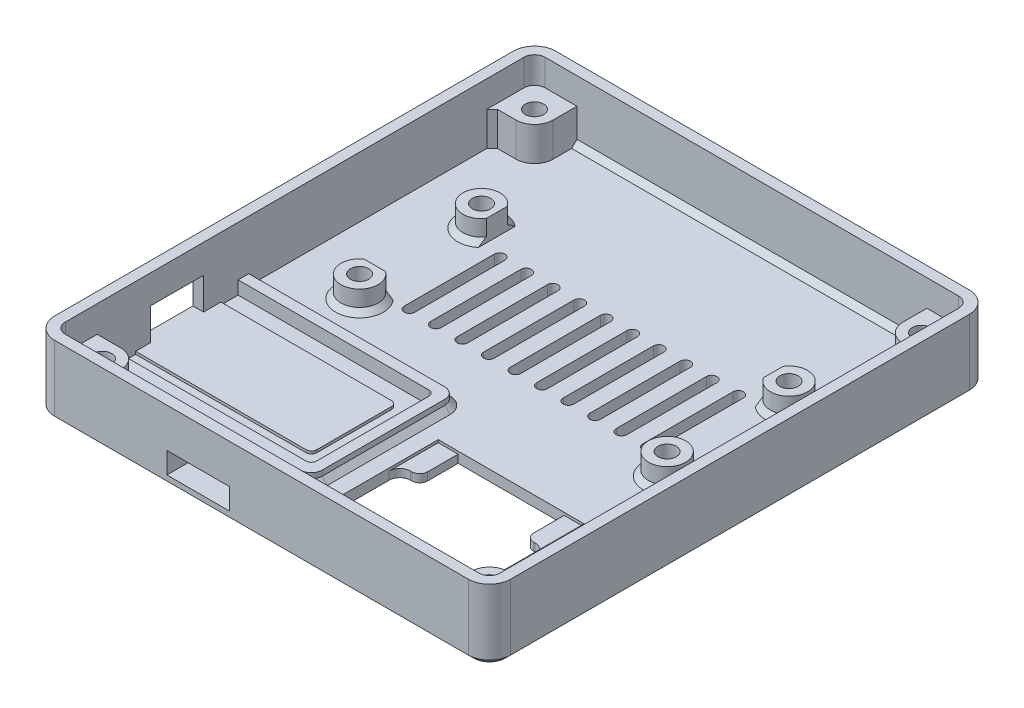
SolidWorks part; units mm, degrees
ref_plane "Front Plane" through (0, 0, 0) normal (0, 0, 1) x (1, 0, 0)
ref_plane "Top Plane" through (0, 0, 0) normal (0, 1, 0) x (1, 0, 0)
ref_plane "Right Plane" through (0, 0, 0) normal (1, 0, 0) x (0, 0, -1)
sketch "Sketch1" plane through (0, 0, 0) normal (0, 1, 0) x (1, 0, 0)
  line L0 (-65.617, -16.3721) -> (-0.617, -16.3721)
  line L1 (-62.117, 10.1279) -> (-4.117, 10.1279)
  line L2 (-62.117, 10.1279) -> (-62.117, -12.8721)
  line L3 (-65.617, 13.6279) -> (-0.617, 13.6279)
  line L4 (-65.617, 13.6279) -> (-65.617, -16.3721)
  line L5 (-62.117, -12.8721) -> (-4.117, -12.8721)
  line L6 (-0.617, 13.6279) -> (-0.617, -16.3721)
  line L7 (-4.117, 10.1279) -> (-4.117, -12.8721)
  line L8 (-24.217, 16.7282) -> (-24.217, 15.4455)
  line L9 (-11.617, 16.7282) -> (-11.617, 15.4455)
  dimension "D1" = 65
  dimension "D2" = 30
  dimension "D3" = 58
  dimension "D4" = 23
  dimension "D5" = 3.5
  dimension "D6" = 3.5
sketch "Sketch2" plane through (0, 0, 0) normal (0, 1, 0) x (1, 0, 0)
  line L0 (-0.617, 13.6279) -> (-0.617, -16.3721) construction
  line L6 (-74.617, 13.6279) -> (-74.617, -16.3721)
  line L7 (-74.617, 30.6279) -> (-74.617, -55.8721)
  line L10 (-72.617, -57.8721) -> (5.383, -57.8721)
  line L11 (-76.617, -1.6221) -> (-76.617, -55.8721)
  line L14 (7.383, 30.6279) -> (7.383, -55.8721)
  line L15 (-72.617, 32.6279) -> (5.383, 32.6279)
  line L16 (-72.617, -59.8721) -> (5.383, -59.8721)
  line L17 (9.383, 30.6279) -> (9.383, -1.6221)
  line L18 (-72.617, 34.6279) -> (5.383, 34.6279)
  line L24 (-76.617, 30.6279) -> (-76.617, -55.8721) construction
  line L25 (-76.617, 30.6279) -> (-76.617, -1.6221)
  line L26 (9.383, 30.6279) -> (9.383, -55.8721) construction
  line L27 (9.383, -1.6221) -> (9.383, -55.8721)
  line L28 (-65.617, 13.6279) -> (-0.617, 13.6279) construction
  line L29 (-65.617, -16.3721) -> (-0.617, -16.3721) construction
  arc A0 (-72.617, -57.8721) -> (-74.617, -55.8721) centre (-72.617, -55.8721) cw
  arc A1 (5.383, -57.8721) -> (7.383, -55.8721) centre (5.383, -55.8721) ccw
  arc A2 (7.383, 30.6279) -> (5.383, 32.6279) centre (5.383, 30.6279) ccw
  arc A3 (-72.617, 32.6279) -> (-74.617, 30.6279) centre (-72.617, 30.6279) ccw
  arc A4 (-72.617, -59.8721) -> (-76.617, -55.8721) centre (-72.617, -55.8721) cw
  arc A5 (5.383, -59.8721) -> (9.383, -55.8721) centre (5.383, -55.8721) ccw
  arc A6 (9.383, 30.6279) -> (5.383, 34.6279) centre (5.383, 30.6279) ccw
  arc A7 (-72.617, 34.6279) -> (-76.617, 30.6279) centre (-72.617, 30.6279) ccw
  point P62 (-76.617, -11.6221)
  point P67 (9.383, -31.6221)
  dimension "D4" = 19
  dimension "D2" = 8
  dimension "D14" = 41.5
  dimension "D1" = 9
  dimension "D5" = 2
extrude "Boss-Extrude1" add sketch "Sketch2" along normal blind 13.4 contours L17 A6 L18 A7 L25 L11 A4 L16 A5 L27 A3 L15 A2 L14 A1 L10 A0 L7 region at (-75.3392, 0, -14.5029)
extrude "Boss-Extrude2" add sketch "Sketch2<3>" along normal blind 2 contours L15 A3 L7 A0 L10 A1 L14 A2 region at (-33.617, 0, 12.6221)
sketch "Sketch2<3>" plane through (0, 0, 0) normal (0, 1, 0) x (1, 0, 0) same geometry as "Sketch2"
sketch "Sketch4" plane through (0, 2, 0) normal (0, 1, 0) x (1, 0, 0)
  line L0 (-59.2343, 12.1129) -> (-59.2343, 8.1428)
  line L9 (-64.1397, -10.0158) -> (-60.0943, -10.0158)
  line L12 (-7.0825, 11.9868) -> (-7.0825, 8.269)
  arc A0 (-7.0825, 8.269) -> (-7.0825, 11.9868) centre (-4.117, 10.1279) ccw
  arc A1 (-7.0825, 8.269) -> (-0.617, 10.1279) centre (-4.117, 10.1279) ccw
  arc A2 (-64.1397, -10.0158) -> (-60.0943, -10.0158) centre (-62.117, -12.8721) ccw
  arc A3 (-65.617, 10.1279) -> (-59.2343, 8.1428) centre (-62.117, 10.1279) ccw
  arc A4 (-59.2343, 12.1129) -> (-59.2343, 8.1428) centre (-62.117, 10.1279) ccw
  circle A5 centre (-4.117, -12.8721) radius 3.5
extrude "Boss-Extrude3" add sketch "Sketch4" along normal offset from surface (4 mm away) 7.4 contours L12 A0 | L0 A4 A3 | L9 A2 | A5 region at (-62.2586, 2, -10.1279) region at (-62.117, 2, 13.0224) region at (-4.0017, 2, -10.1279) region at (-4.117, 2, 12.8721) up to face at (-33.617, 13.4, 12.6221)
hole_wizard "CSK for #4 Flat Head Socket Cap Screw1" positions "Sketch6" profile "Sketch5" countersink size "#4" standard "ANSI Inch" end condition through all
sketch "Sketch6" plane through (0, 0, 0) normal (0, -1, 0) x (-1, 0, 0)
  point P0 (4.117, 10.1279)
  point P4 (62.117, 10.1279)
  point P8 (4.117, -12.8721)
  point P12 (62.117, -12.8721)
sketch "Sketch5" plane through (-4.117, 0, -10.1279) normal (1, 0, 0) x (0, 0, -1)
  line L0 (0, 0) -> (0, 13.4)
  line L1 (0, 13.4) -> (1.7272, 13.4)
  line L2 (1.7272, 13.4) -> (1.7272, 1.8805)
  line L3 (1.7272, 1.8805) -> (3.3619, 0)
  line L5 (3.3619, 0) -> (0, 0)
  line L6 (-1.7272, 1.8805) -> (-3.3619, 0) construction
  line L11 (0, -6.35) -> (0, 107.95) construction
  dimension "Thru Hole Dia." = 3.4544
  dimension "Thru Hole Depth" = 13.4
  dimension "Near C'Sink Dia." = 6.7237
  dimension "Near C'Sink Angle" = 82
sketch "Sketch15" plane through (0, 2, 0) normal (0, 1, 0) x (1, 0, 0)
  line L1 (-74.617, -23.279) -> (-37.617, -23.279)
  line L2 (-74.617, -21.279) -> (-74.617, -23.279)
  line L3 (-74.617, -46.479) -> (-37.617, -46.479)
  line L4 (-37.617, -23.279) -> (-37.617, -46.479)
  line L5 (-74.617, -21.279) -> (-35.617, -21.279)
  line L6 (-35.617, -21.279) -> (-35.617, -48.479)
  line L7 (-74.617, -48.479) -> (-35.617, -48.479)
  line L8 (-74.617, -46.479) -> (-74.617, -48.479)
  dimension "D1" = 23.2
extrude "Boss-Extrude5" add sketch "Sketch15" along normal blind 2
fillet "Fillet1" radius 1 1 edges at (-37.617, 3, 23.279)
fillet "Fillet2" radius 1 1 edges at (-37.617, 3, 46.479)
fillet "Fillet3" radius 2 2 edges at (-35.617, 3, 48.479) (-35.617, 3, 21.279)
sketch "Sketch16" plane through (-74.617, 0, 0) normal (1, 0, 0) x (0, 0, -1)
  line L1 (-39.8053, 2) -> (-29.8053, 2)
  line L2 (-39.8053, 2) -> (-39.8053, 8)
  line L3 (-39.8053, 8) -> (-29.8053, 8)
  line L4 (-29.8053, 2) -> (-29.8053, 8)
  dimension "D1" = 6
  dimension "D2" = 10
extrude "Cut-Extrude4" cut sketch "Sketch16" against normal up to next
sketch "Sketch9" plane through (0, 2, 0) normal (0, 1, 0) x (1, 0, 0)
  line L0 (7.383, 30.6279) -> (7.383, -55.8721) construction
  line L1 (2.883, -49.8721) -> (7.383, -49.8721)
  line L2 (-0.617, 32.6279) -> (5.383, 32.6279)
  line L3 (7.3733, 24.6279) -> (7.383, 30.6246)
  line L4 (-0.617, -53.3721) -> (-0.617, -57.8721)
  line L5 (-66.617, 32.6279) -> (-72.617, 32.6279)
  line L6 (-0.617, 28.1279) -> (-0.617, 32.6279)
  line L7 (-0.617, -57.8721) -> (5.383, -57.8721)
  line L8 (2.883, 24.6279) -> (7.3733, 24.6279)
  line L9 (7.383, -49.8721) -> (7.383, -55.8721)
  line L10 (-66.617, -53.3721) -> (-66.617, -57.8721)
  line L11 (-74.6073, -49.8721) -> (-74.617, -55.8689)
  line L12 (-70.117, 24.6279) -> (-74.617, 24.6279)
  line L13 (-66.617, 28.1279) -> (-66.617, 32.6279)
  line L14 (-70.117, -49.8721) -> (-74.6073, -49.8721)
  line L15 (-66.617, -57.8721) -> (-72.617, -57.8721)
  line L16 (-74.617, 24.6279) -> (-74.617, 30.6279)
  line L18 (-72.617, -57.8721) -> (5.383, -57.8721) construction
  arc A0 (2.883, -49.8721) -> (-0.617, -53.3721) centre (2.883, -53.3721) ccw
  arc A1 (5.383, 32.6279) -> (7.383, 30.6246) centre (5.383, 30.6279) cw
  arc A2 (7.383, -55.8721) -> (5.383, -57.8721) centre (5.383, -55.8721) cw
  arc A3 (-0.617, 28.1279) -> (2.883, 24.6279) centre (2.883, 28.1279) ccw
  arc A4 (-72.617, -57.8721) -> (-74.617, -55.8689) centre (-72.617, -55.8721) cw
  arc A5 (-70.117, 24.6279) -> (-66.617, 28.1279) centre (-70.117, 28.1279) ccw
  arc A6 (-74.617, 30.6279) -> (-72.617, 32.6279) centre (-72.617, 30.6279) cw
  arc A7 (-66.617, -53.3721) -> (-70.117, -49.8721) centre (-70.117, -53.3721) ccw
  dimension "D1" = 4.5
  dimension "D2" = 2
  dimension "D3" = 2
extrude "Boss-Extrude4" add sketch "Sketch9" along normal offset from surface (6.4 mm away) 5 up to face at (-33.617, 13.4, 12.6221)
chamfer "Chamfer1" distance 1 angle 45 4 edges at (-0.617, 5.2, 57.8721) (7.383, 5.2, 49.8721) (-74.617, 5.2, -24.6279) (-66.617, 5.2, 57.8721)
chamfer "Chamfer2" distance 1 angle 45 15 edges at (-62.117, 2, 16.3721) (-65.617, 2, -10.1279) (7.383, 2, 9.1238) (-33.617, 2, 57.8721) (-33.617, 2, -32.6279) (-0.617, 2, -10.1279) (-0.617, 2, 55.1221) (0.4081, 2, 50.8973) (-4.117, 2, 16.3721) (-56.117, 2, 48.479) (-56.117, 2, 21.279) (-36.2028, 2, 47.8932) (-36.2028, 2, 21.8648) (-35.617, 2, 34.879) (4.633, 2, 49.8721)
chamfer "Chamfer3" distance 1 angle 45 6 edges at (8.2114, 0, 58.7006) (-75.4454, 0, 58.7006) (8.2114, 0, -33.4563) (-76.617, 0, 12.6221) (-75.4454, 0, -33.4563) (-33.617, 0, -34.6279) tangent propagation no
sketch "Sketch12" plane through (0, 0, 0) normal (0, -1, 0) x (1, 0, 0)
  line L0 (-55.6605, 9.9113) -> (-55.6605, -7.0887) construction
  line L1 (-54.6605, 9.9113) -> (-54.6605, -7.0887)
  line L2 (-56.6605, 9.9113) -> (-56.6605, -7.0887)
  line L3 (-50.6605, 9.9113) -> (-50.6605, -7.0887) construction
  line L4 (-49.6605, 9.9113) -> (-49.6605, -7.0887)
  line L5 (-51.6605, 9.9113) -> (-51.6605, -7.0887)
  line L6 (-45.6605, 9.9113) -> (-45.6605, -7.0887) construction
  line L7 (-44.6605, 9.9113) -> (-44.6605, -7.0887)
  line L8 (-46.6605, 9.9113) -> (-46.6605, -7.0887)
  line L9 (-40.6605, 9.9113) -> (-40.6605, -7.0887) construction
  line L10 (-39.6605, 9.9113) -> (-39.6605, -7.0887)
  line L11 (-41.6605, 9.9113) -> (-41.6605, -7.0887)
  line L12 (-35.6605, 9.9113) -> (-35.6605, -7.0887) construction
  line L13 (-34.6605, 9.9113) -> (-34.6605, -7.0887)
  line L14 (-36.6605, 9.9113) -> (-36.6605, -7.0887)
  line L15 (-30.6605, 9.9113) -> (-30.6605, -7.0887) construction
  line L16 (-29.6605, 9.9113) -> (-29.6605, -7.0887)
  line L17 (-31.6605, 9.9113) -> (-31.6605, -7.0887)
  line L18 (-25.6605, 9.9113) -> (-25.6605, -7.0887) construction
  line L19 (-24.6605, 9.9113) -> (-24.6605, -7.0887)
  line L20 (-26.6605, 9.9113) -> (-26.6605, -7.0887)
  line L21 (-20.6605, 9.9113) -> (-20.6605, -7.0887) construction
  line L22 (-19.6605, 9.9113) -> (-19.6605, -7.0887)
  line L23 (-21.6605, 9.9113) -> (-21.6605, -7.0887)
  line L24 (-15.6605, 9.9113) -> (-15.6605, -7.0887) construction
  line L25 (-14.6605, 9.9113) -> (-14.6605, -7.0887)
  line L26 (-16.6605, 9.9113) -> (-16.6605, -7.0887)
  line L27 (-10.6605, 9.9113) -> (-10.6605, -7.0887) construction
  line L28 (-9.6605, 9.9113) -> (-9.6605, -7.0887)
  line L29 (-11.6605, 9.9113) -> (-11.6605, -7.0887)
  arc A0 (-54.6605, 9.9113) -> (-56.6605, 9.9113) centre (-55.6605, 9.9113) ccw
  arc A1 (-56.6605, -7.0887) -> (-54.6605, -7.0887) centre (-55.6605, -7.0887) ccw
  arc A2 (-49.6605, 9.9113) -> (-51.6605, 9.9113) centre (-50.6605, 9.9113) ccw
  arc A3 (-51.6605, -7.0887) -> (-49.6605, -7.0887) centre (-50.6605, -7.0887) ccw
  arc A4 (-44.6605, 9.9113) -> (-46.6605, 9.9113) centre (-45.6605, 9.9113) ccw
  arc A5 (-46.6605, -7.0887) -> (-44.6605, -7.0887) centre (-45.6605, -7.0887) ccw
  arc A6 (-39.6605, 9.9113) -> (-41.6605, 9.9113) centre (-40.6605, 9.9113) ccw
  arc A7 (-41.6605, -7.0887) -> (-39.6605, -7.0887) centre (-40.6605, -7.0887) ccw
  arc A8 (-34.6605, 9.9113) -> (-36.6605, 9.9113) centre (-35.6605, 9.9113) ccw
  arc A9 (-36.6605, -7.0887) -> (-34.6605, -7.0887) centre (-35.6605, -7.0887) ccw
  arc A10 (-29.6605, 9.9113) -> (-31.6605, 9.9113) centre (-30.6605, 9.9113) ccw
  arc A11 (-31.6605, -7.0887) -> (-29.6605, -7.0887) centre (-30.6605, -7.0887) ccw
  arc A12 (-24.6605, 9.9113) -> (-26.6605, 9.9113) centre (-25.6605, 9.9113) ccw
  arc A13 (-26.6605, -7.0887) -> (-24.6605, -7.0887) centre (-25.6605, -7.0887) ccw
  arc A14 (-19.6605, 9.9113) -> (-21.6605, 9.9113) centre (-20.6605, 9.9113) ccw
  arc A15 (-21.6605, -7.0887) -> (-19.6605, -7.0887) centre (-20.6605, -7.0887) ccw
  arc A16 (-14.6605, 9.9113) -> (-16.6605, 9.9113) centre (-15.6605, 9.9113) ccw
  arc A17 (-16.6605, -7.0887) -> (-14.6605, -7.0887) centre (-15.6605, -7.0887) ccw
  arc A18 (-9.6605, 9.9113) -> (-11.6605, 9.9113) centre (-10.6605, 9.9113) ccw
  arc A19 (-11.6605, -7.0887) -> (-9.6605, -7.0887) centre (-10.6605, -7.0887) ccw
  point P2 (-55.6605, 1.4113)
  point P10 (-50.6605, 1.4113)
  point P17 (-45.6605, 1.4113)
  point P24 (-40.6605, 1.4113)
  point P31 (-35.6605, 1.4113)
  point P38 (-30.6605, 1.4113)
  point P45 (-25.6605, 1.4113)
  point P52 (-20.6605, 1.4113)
  point P59 (-15.6605, 1.4113)
  point P66 (-10.6605, 1.4113)
  dimension "D1" = 2
  dimension "D2" = 17
  dimension "D3" = 10
extrude "Cut-Extrude2" cut sketch "Sketch12" against normal up to next
sketch "Sketch19" plane through (-134.4891, 0, 57.8721) normal (0, 0, -1) x (-1, 0, 0)
  line L1 (-94.8286, 6) -> (-83.0286, 6)
  line L2 (-94.8286, 6) -> (-94.8286, 2)
  line L3 (-94.8286, 2) -> (-83.0286, 2)
  line L4 (-83.0286, 6) -> (-83.0286, 2)
  dimension "D1" = 4
  dimension "D2" = 11.8
extrude "Cut-Extrude6" cut sketch "Sketch19" against normal through all and the other way blind 2
sketch "Sketch21" plane through (0, 2, 0) normal (0, 1, 0) x (1, 0, 0)
  line L0 (-74.617, -23.279) -> (-74.617, -29.8053) construction
  line L1 (-74.617, -26.5421) -> (-42.4496, -26.5421)
  line L3 (-74.617, -42.6194) -> (-42.4496, -42.6194)
  line L4 (-41.4496, -27.5421) -> (-41.4496, -41.6194)
  line L5 (-74.617, -42.6194) -> (-74.617, -46.4053)
  line L6 (-74.617, -23.279) -> (-38.7303, -23.279)
  line L7 (-74.617, -23.279) -> (-74.617, -26.5421)
  line L8 (-74.617, -46.4053) -> (-38.7303, -46.4053)
  line L9 (-37.7303, -24.279) -> (-37.7303, -45.4053)
  arc A0 (-41.4496, -27.5421) -> (-42.4496, -26.5421) centre (-42.4496, -27.5421) ccw
  arc A1 (-42.4496, -42.6194) -> (-41.4496, -41.6194) centre (-42.4496, -41.6194) ccw
  arc A2 (-37.7303, -45.4053) -> (-38.7303, -46.4053) centre (-38.7303, -45.4053) cw
  arc A3 (-37.7303, -24.279) -> (-38.7303, -23.279) centre (-38.7303, -24.279) ccw
  dimension "D1" = 1
extrude "Cut-Extrude8" cut sketch "Sketch21" against normal blind 0.5
sketch "Sketch22" plane through (0, 0, 57.8721) normal (0, 0, -1) x (-1, 0, 0)
  line L0 (38.1605, 7.5) -> (38.1605, 2)
  line L1 (39.6605, 6) -> (51.4605, 6)
  line L2 (39.6605, 6) -> (39.6605, 2)
  line L3 (52.9605, 7.5) -> (52.9605, 0.5) construction
  line L4 (51.4605, 6) -> (51.4605, 2)
  line L6 (52.9605, 7.5) -> (52.9605, 2)
  line L7 (38.1605, 7.5) -> (52.9605, 7.5)
  line L8 (39.6605, 2) -> (38.1605, 2)
  line L9 (0.617, 2) -> (66.617, 2) construction
  line L10 (51.4605, 2) -> (52.9605, 2)
  line L11 (38.1605, 7.5) -> (38.1605, 0.5) construction
  line L12 (38.1605, 0.5) -> (52.9605, 0.5) construction
  line L13 (39.6605, 2) -> (51.4605, 2) construction
  dimension "D1" = 1.5
extrude "Boss-Extrude7" add sketch "Sketch22" along normal blind 2
hole_wizard "CSK for #4 Flat Head Socket Cap Screw2" positions "Sketch23" profile "Sketch25" countersink size "#4" standard "ANSI Inch" end condition through all
sketch "Sketch23" plane through (0, 0, 0) normal (0, -1, 0) x (-1, 0, 0)
  point P0 (70.117, -53.3721)
  point P4 (-2.883, -53.3721)
  point P8 (70.117, 28.1279)
  point P11 (-2.883, 28.1279)
sketch "Sketch25" plane through (-70.117, 0, 53.3721) normal (1, 0, 0) x (0, 0, -1)
  line L0 (0, 0) -> (0, 13.4)
  line L1 (0, 13.4) -> (1.7272, 13.4)
  line L2 (1.7272, 13.4) -> (1.7272, 1.8805)
  line L3 (1.7272, 1.8805) -> (3.3619, 0)
  line L5 (3.3619, 0) -> (0, 0)
  line L6 (-1.7272, 1.8805) -> (-3.3619, 0) construction
  line L11 (0, -6.35) -> (0, 107.95) construction
  dimension "Thru Hole Dia." = 3.4544
  dimension "Thru Hole Depth" = 13.4
  dimension "Near C'Sink Dia." = 6.7238
  dimension "Near C'Sink Angle" = 82
sketch "Sketch26" plane through (0, 2, 0) normal (0, 1, 0) x (1, 0, 0)
  line L1 (-4.1349, -28.5116) -> (-31.6349, -28.5116)
  line L2 (-4.1349, -28.5116) -> (-4.1349, -56.0116)
  line L3 (-4.1349, -56.0116) -> (-31.6349, -56.0116)
  line L4 (-31.6349, -28.5116) -> (-31.6349, -56.0116)
  dimension "D1" = 27.5
  dimension "D2" = 27.5
extrude "Cut-Extrude9" cut sketch "Sketch26" against normal blind 0.5
sketch "Sketch27" plane through (0, 1.5, 0) normal (0, 1, 0) x (1, 0, 0)
  line L0 (-27.8849, -28.5116) -> (-7.8849, -28.5116)
  line L1 (-27.8849, -28.5116) -> (-27.8849, -34.2616)
  line L2 (-27.8849, -56.0116) -> (-7.8849, -56.0116)
  line L3 (-7.8849, -28.5116) -> (-7.8849, -34.2616)
  line L4 (-6.3849, -48.7616) -> (-6.1349, -48.7616)
  line L5 (-29.6349, -35.7616) -> (-29.3849, -35.7616)
  line L6 (-31.6349, -37.7616) -> (-31.6349, -46.7616)
  line L7 (-29.6349, -48.7616) -> (-29.3849, -48.7616)
  line L8 (-7.8849, -50.2616) -> (-7.8849, -56.0116)
  line L9 (-6.3849, -35.7616) -> (-6.1349, -35.7616)
  line L10 (-4.1349, -37.7616) -> (-4.1349, -46.7616)
  line L11 (-27.8849, -50.2616) -> (-27.8849, -56.0116)
  arc A0 (-6.1349, -48.7616) -> (-4.1349, -46.7616) centre (-6.1349, -46.7616) ccw
  arc A1 (-4.1349, -37.7616) -> (-6.1349, -35.7616) centre (-6.1349, -37.7616) ccw
  arc A2 (-29.6349, -48.7616) -> (-31.6349, -46.7616) centre (-29.6349, -46.7616) cw
  arc A3 (-31.6349, -37.7616) -> (-29.6349, -35.7616) centre (-29.6349, -37.7616) cw
  arc A4 (-27.8849, -50.2616) -> (-29.3849, -48.7616) centre (-29.3849, -50.2616) ccw
  arc A5 (-7.8849, -50.2616) -> (-6.3849, -48.7616) centre (-6.3849, -50.2616) cw
  arc A6 (-7.8849, -34.2616) -> (-6.3849, -35.7616) centre (-6.3849, -34.2616) ccw
  arc A7 (-27.8849, -34.2616) -> (-29.3849, -35.7616) centre (-29.3849, -34.2616) cw
  dimension "D3" = 2
  dimension "D4" = 1.5
  dimension "D1" = 13
  dimension "D2" = 13
extrude "Cut-Extrude10" cut sketch "Sketch27" against normal through all
